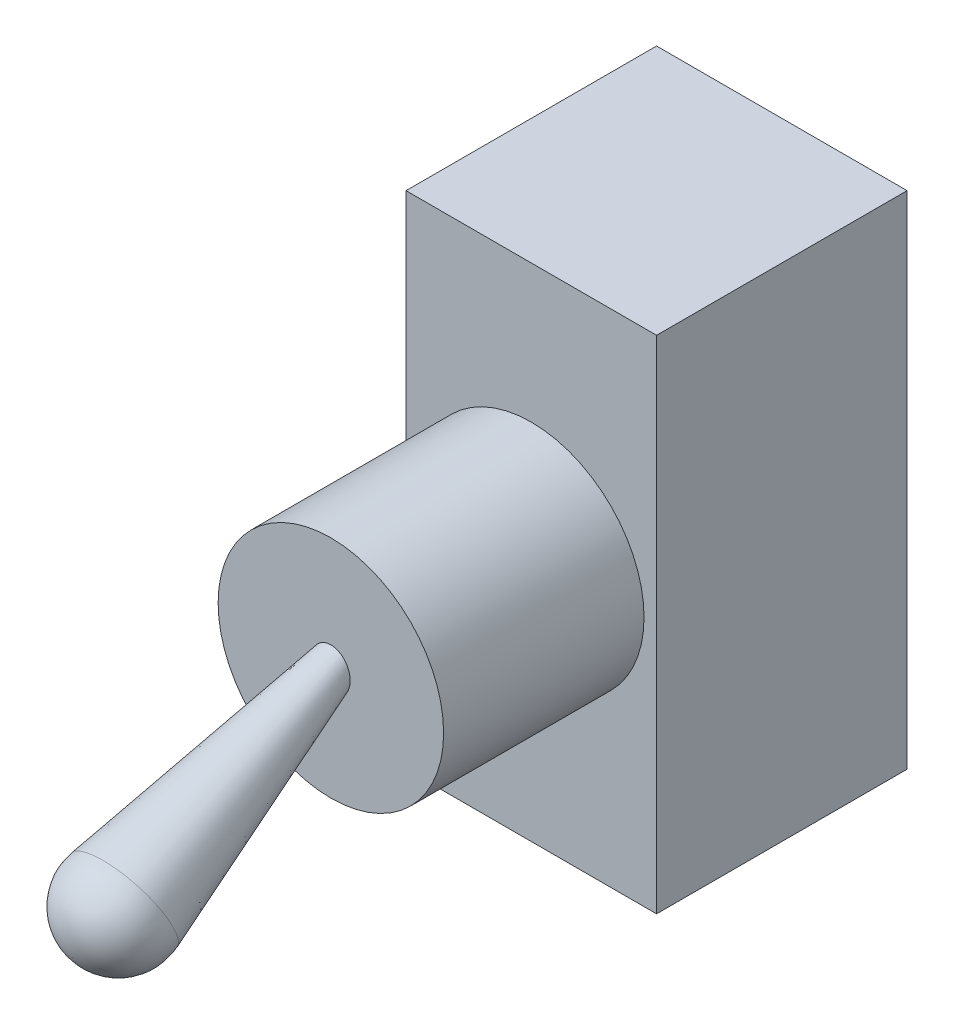
SolidWorks part; units mm, degrees
ref_plane "Front Plane" through (0, 0, 0) normal (0, 0, 1) x (1, 0, 0)
ref_plane "Top Plane" through (0, 0, 0) normal (0, 1, 0) x (1, 0, 0)
ref_plane "Right Plane" through (0, 0, 0) normal (1, 0, 0) x (0, 0, -1)
sketch "Sketch1" plane through (0, 0, 0) normal (0, 0, 1) x (1, 0, 0)
  line L1 (-6.35, 12.7) -> (6.35, 12.7)
  line L2 (-6.35, 12.7) -> (-6.35, -12.7)
  line L3 (-6.35, -12.7) -> (6.35, -12.7)
  line L4 (6.35, 12.7) -> (6.35, -12.7)
  line L5 (-6.35, 12.7) -> (6.35, -12.7) construction
  line L6 (-6.35, -12.7) -> (6.35, 12.7) construction
  circle A0 centre (0, 0) radius 5.715
  point P0 (0, 0)
  dimension "D3" = 11.43
  dimension "D1" = 12.7
  dimension "D2" = 25.4
extrude "Extrude1" add sketch "Sketch1" against normal blind 12.7 contours L4 L3 L2 L1
extrude "Extrude2" add sketch "Sketch1<3>" along normal blind 10.16 contours A0 region at (0, 0, 0)
sketch "Sketch1<3>" plane through (0, 0, 0) normal (0, 0, 1) x (1, 0, 0) same geometry as "Sketch1"
sketch "Sketch2" plane through (0, 0, 0) normal (1, 0, 0) x (0, 0, -1)
  line L0 (-10.16, 0) -> (-23.2431, -6.1812) construction
  line L1 (-10.16, 5.715) -> (-10.16, -5.715) construction
  line L2 (-10.16, 1.0161) -> (-24.4915, -3.5389)
  line L3 (-23.2431, -6.1812) -> (-24.4915, -3.5389)
  line L4 (-10.16, 1.0161) -> (-10.16, 0)
  line L5 (-10.16, 0) -> (-23.2431, -6.1812)
revolve "Revolve1" add sketch "Sketch2" angle 360 about L0
fillet "Fillet1" radius 2.54 1 edges at (0, -3.5389, 24.4915)
